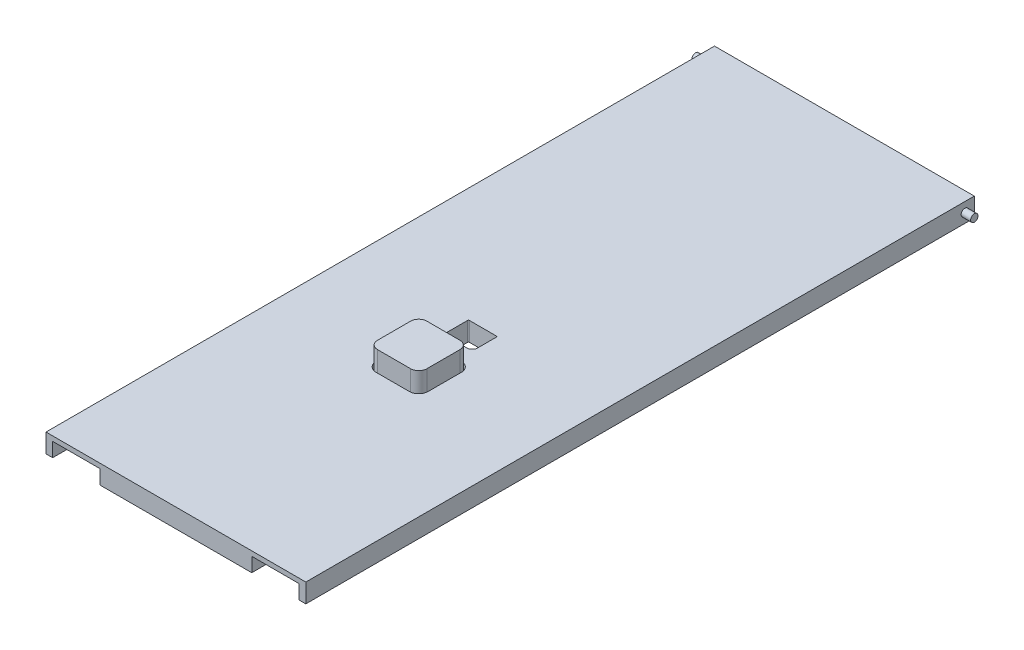
SolidWorks part; units mm, degrees
note: The reader was unsure of these and kept them because the rebuilt part matched: shared geometry of "草图6<3>".
material "PLA"
ref_plane "前视基准面" through (0, 0, 0) normal (0, 0, 1) x (1, 0, 0)
ref_plane "上视基准面" through (0, 0, 0) normal (0, 1, 0) x (1, 0, 0)
ref_plane "右视基准面" through (0, 0, 0) normal (1, 0, 0) x (0, 0, -1)
sketch "草图1" plane through (0, 0, 0) normal (0, 0, 1) x (1, 0, 0)
  line L21 (-13.7, 0) -> (13.7, 0)
  line L24 (13.7, 0) -> (13.7, 2)
  line L25 (13.7, 2) -> (-13.7, 2)
  line L26 (-13.7, 2) -> (-13.7, 0)
  point P0 (0, 0)
  dimension "D1" = 27.4
  dimension "D2" = 2
extrude "凸台-拉伸1" add sketch "草图1" along normal blind 70.5
ref_plane "基准面1" through (0, 0, 0) normal (1, 0, 0) x (0, 0, -1)
sketch "草图13" plane through (0, 0, 0) normal (1, 0, 0) x (0, 0, -1)
  line L0 (-68.5, 0) -> (-67.1502, 0)
  line L1 (-70.5, 0) -> (0, 0) construction
  line L2 (-67.1502, 0) -> (-67.1502, 1.65)
  line L3 (-68.5, 0) -> (-68.5, -1)
  line L4 (-68.5, -1) -> (-68, -1)
  line L5 (-68, -1) -> (-68, 1)
  line L10 (-68.5, 0) -> (-68.9362, 0)
  line L11 (-67.1502, 1.65) -> (-68.65, 1.65)
  line L12 (-68.9362, 0) -> (-68.9362, 0.4164)
  arc A2 (-68, 1) -> (-68.9362, 0.4164) centre (-68.65, 1) ccw
  arc A3 (-68.5, 0) -> (-68.9362, 0.4164) centre (-69.3765, -0.4815) ccw
  arc A4 (-68.65, 1.65) -> (-68.9362, 0.4164) centre (-68.65, 1) ccw
  dimension "D2" = 1.3498
  dimension "D3" = 1.65
  dimension "D1" = 0
extrude "切除-拉伸5" cut sketch "草图13" against normal mid plane 5
fillet "圆角4" radius 0.1 1 edges at (0, 0, 68.9362)
sketch "草图14" plane through (-13.7, 0, 0) normal (-1, 0, 0) x (0, 0, 1)
  line L0 (1.4, 2) -> (1.4, 1) construction
  line L1 (0.6, 1) -> (0.6, 2) construction
  line L2 (1.4, 2) -> (1.4, 1)
  line L3 (0.6, 1) -> (0.6, 2)
  arc A0 (0.6, 1) -> (1.4, 1) centre (1, 1) ccw construction
  arc A1 (0.6, 1) -> (1.4, 1) centre (1, 1) ccw
  circle A2 centre (1, 1) radius 0.39
  dimension "D1" = 0.78
extrude "凸台-拉伸7" add sketch "草图14" along normal blind 1 contours A2
sketch "草图15" plane through (13.7, 0, 0) normal (1, 0, 0) x (0, 0, -1)
  circle A0 centre (-1, 1) radius 0.39 construction
  circle A1 centre (-1, 1) radius 0.39
extrude "凸台-拉伸8" add sketch "草图15" along normal blind 1
sketch "草图16" plane through (0, 0, 70.5) normal (0, 0, 1) x (1, 0, 0)
  line L0 (0, 0) -> (0, 2) construction
  line L1 (13.7, 2) -> (-13.7, 2) construction
  line L2 (-13.7, 0) -> (13.7, 0) construction
  line L3 (-13, 1.5) -> (-8, 1.5)
  line L4 (-13, 1.5) -> (-13, 0)
  line L5 (-13, 0) -> (-8, 0)
  line L6 (-8, 1.5) -> (-8, 0)
  line L7 (13, 0) -> (8, 0)
  line L8 (8, 1.5) -> (8, 0)
  line L9 (13, 1.5) -> (8, 1.5)
  line L10 (13, 1.5) -> (13, 0)
  dimension "D1" = 8
  dimension "D2" = 5
  dimension "D3" = 1.5
extrude "切除-拉伸6" cut sketch "草图16" against normal blind 5
sketch "草图4" plane through (0, 2, 0) normal (0, 1, 0) x (1, 0, 0)
  line L0 (1.8997, -42.991) -> (-1.9003, -46.791) construction
  line L2 (-2.7503, -42.141) -> (2.7497, -42.141)
  line L3 (-2.7503, -42.141) -> (-2.7503, -47.641)
  line L4 (-2.7503, -47.641) -> (2.7497, -47.641)
  line L5 (2.7497, -42.141) -> (2.7497, -47.641)
  line L6 (-2.7503, -42.141) -> (2.7497, -47.641) construction
  line L7 (-2.7503, -47.641) -> (2.7497, -42.141) construction
  line L8 (1.2997, -47.391) -> (2.4997, -46.191)
  line L9 (2.4997, -46.191) -> (2.4997, -43.591)
  line L10 (2.4997, -43.591) -> (1.2997, -42.391)
  line L11 (1.2997, -42.391) -> (-1.3003, -42.391)
  line L12 (-1.3003, -42.391) -> (-2.5003, -43.591)
  line L13 (-2.5003, -43.591) -> (-2.5003, -46.191)
  line L14 (-2.5003, -46.191) -> (-1.3003, -47.391)
  line L15 (-1.3003, -47.391) -> (1.2997, -47.391)
  line L16 (1.2997, -47.391) -> (2.4997, -46.191) construction
  line L17 (2.4997, -46.191) -> (2.4997, -43.591) construction
  line L18 (2.4997, -43.591) -> (1.2997, -42.391) construction
  line L19 (1.2997, -42.391) -> (-1.3003, -42.391) construction
  line L20 (-1.3003, -42.391) -> (-2.5003, -43.591) construction
  line L21 (-2.5003, -43.591) -> (-2.5003, -46.191) construction
  line L22 (-2.5003, -46.191) -> (-1.3003, -47.391) construction
  line L23 (-1.3003, -47.391) -> (1.2997, -47.391) construction
  point P6 (-0.0003, -44.891)
  dimension "D2" = 5.5
  dimension "D1" = 0
extrude "切除-拉伸2" cut sketch "草图4" against normal through all
fillet "圆角1" radius 1 4 edges at (-2.7503, 1, 47.641) (2.7497, 1, 47.641) (2.7497, 1, 42.141) (-2.7503, 1, 42.141)
sketch "草图5" plane through (0, 0, 0) normal (0, -1, 0) x (1, 0, 0)
  line L0 (-2.6003, 46.641) -> (-2.6003, 43.141)
  line L1 (-1.7503, 42.291) -> (1.7497, 42.291)
  line L2 (2.5997, 43.141) -> (2.5997, 46.641)
  line L3 (1.7497, 47.491) -> (-1.7503, 47.491)
  line L4 (-2.7503, 46.641) -> (-2.7503, 43.141)
  line L5 (1.7497, 47.641) -> (-1.7503, 47.641)
  line L6 (2.7497, 43.141) -> (2.7497, 46.641)
  line L7 (-1.7503, 42.141) -> (1.7497, 42.141)
  line L8 (-2.7503, 46.641) -> (-2.7503, 43.141) construction
  line L9 (1.7497, 47.641) -> (-1.7503, 47.641) construction
  line L10 (2.7497, 43.141) -> (2.7497, 46.641) construction
  line L11 (-1.7503, 42.141) -> (1.7497, 42.141) construction
  arc A0 (-2.6003, 43.141) -> (-1.7503, 42.291) centre (-1.7503, 43.141) ccw
  arc A1 (1.7497, 42.291) -> (2.5997, 43.141) centre (1.7497, 43.141) ccw
  arc A2 (2.5997, 46.641) -> (1.7497, 47.491) centre (1.7497, 46.641) ccw
  arc A3 (-1.7503, 47.491) -> (-2.6003, 46.641) centre (-1.7503, 46.641) ccw
  arc A4 (-1.7503, 47.641) -> (-2.7503, 46.641) centre (-1.7503, 46.641) ccw
  arc A5 (2.7497, 46.641) -> (1.7497, 47.641) centre (1.7497, 46.641) ccw
  arc A6 (1.7497, 42.141) -> (2.7497, 43.141) centre (1.7497, 43.141) ccw
  arc A7 (-2.7503, 43.141) -> (-1.7503, 42.141) centre (-1.7503, 43.141) ccw
  arc A8 (-1.7503, 47.641) -> (-2.7503, 46.641) centre (-1.7503, 46.641) ccw construction
  arc A9 (2.7497, 46.641) -> (1.7497, 47.641) centre (1.7497, 46.641) ccw construction
  arc A10 (1.7497, 42.141) -> (2.7497, 43.141) centre (1.7497, 43.141) ccw construction
  arc A11 (-2.7503, 43.141) -> (-1.7503, 42.141) centre (-1.7503, 43.141) ccw construction
  dimension "D1" = 0
  dimension "D2" = 0.15
extrude "凸台-拉伸3" add sketch "草图5" against normal blind 4 separate body
sketch "草图6" plane through (0, 0, 0) normal (0, -1, 0) x (1, 0, 0)
  line L0 (-2.0833, 47.423) -> (-4.788, 46.271)
  line L1 (-4.788, 43.5109) -> (-2.0833, 42.3589)
  line L2 (-4.2003, 44.891) -> (-2.6003, 44.891) construction
  line L3 (-0.0003, 42.291) -> (-0.0003, 47.491) construction
  line L5 (-2.6003, 46.641) -> (-2.6003, 43.141)
  line L6 (-1.7503, 42.291) -> (1.7497, 42.291)
  line L7 (2.5997, 43.141) -> (2.5997, 46.641)
  line L12 (1.7497, 47.491) -> (-1.7503, 47.491)
  line L13 (-2.6003, 46.641) -> (-2.6003, 43.141)
  line L14 (-1.7503, 42.291) -> (1.7497, 42.291)
  line L15 (2.5997, 43.141) -> (2.5997, 46.641)
  line L16 (1.7497, 47.491) -> (-1.7503, 47.491)
  line L17 (2.0828, 47.423) -> (4.7875, 46.271)
  line L18 (4.7875, 43.5109) -> (2.0828, 42.3589)
  arc A2 (-4.788, 46.271) -> (-4.788, 43.5109) centre (-4.2003, 44.891) ccw
  circle A12 centre (-4.2003, 44.891) radius 0.9
  circle A13 centre (4.1997, 44.891) radius 0.9
  arc A14 (4.7875, 46.271) -> (4.7875, 43.5109) centre (4.1997, 44.891) cw
  arc A15 (-1.7503, 47.491) -> (-2.6003, 46.641) centre (-1.7503, 46.641) ccw
  arc A16 (-2.6003, 43.141) -> (-1.7503, 42.291) centre (-1.7503, 43.141) ccw
  arc A17 (1.7497, 42.291) -> (2.5997, 43.141) centre (1.7497, 43.141) ccw
  arc A18 (2.5997, 46.641) -> (1.7497, 47.491) centre (1.7497, 46.641) ccw
  arc A19 (-1.7503, 47.491) -> (-2.6003, 46.641) centre (-1.7503, 46.641) ccw
  arc A20 (-2.6003, 43.141) -> (-1.7503, 42.291) centre (-1.7503, 43.141) ccw
  arc A21 (1.7497, 42.291) -> (2.5997, 43.141) centre (1.7497, 43.141) ccw
  arc A22 (2.5997, 46.641) -> (1.7497, 47.491) centre (1.7497, 46.641) ccw
  arc M15 (-1.7503, 47.491) -> (-2.6003, 46.641) centre (-1.7503, 46.641) ccw
  line M16 (-2.6003, 46.641) -> (-2.6003, 43.141)
  arc M17 (-2.6003, 43.141) -> (-1.7503, 42.291) centre (-1.7503, 43.141) ccw
  line M18 (-1.7503, 42.291) -> (1.7497, 42.291)
  arc M19 (1.7497, 42.291) -> (2.5997, 43.141) centre (1.7497, 43.141) ccw
  line M20 (2.5997, 43.141) -> (2.5997, 46.641)
  arc M21 (2.5997, 46.641) -> (1.7497, 47.491) centre (1.7497, 46.641) ccw
  line M22 (1.7497, 47.491) -> (-1.7503, 47.491)
  dimension "D2" = 3
  dimension "D3" = 1.8
  dimension "D4" = 1.6
  dimension "D1" = 0
extrude "凸台-拉伸4" add sketch "草图6" along normal blind 2 contours L0 A2 L1 A12 M17 M16 M15 | M22 M15 M16 M17 M18 M19 M20 M21 | A14 L17 L18 A13 M21 M20 M19
sketch "草图7" plane through (0, 0, 0) normal (0, -1, 0) x (1, 0, 0)
  circle A0 centre (4.1997, 44.891) radius 0.75
  circle A1 centre (-4.2003, 44.891) radius 0.75
  dimension "D1" = 1.5
extrude "凸台-拉伸5" add sketch "草图7" along normal offset from surface (4.5 mm away) 2.5 up to face at (-0.0003, -2, 44.891) offset beyond the face yes
extrude "凸台-拉伸6" add sketch "草图6<3>" along normal blind 3 from surface at 2 starting at face at (-0.0003, -2, 44.891)
sketch "草图6<3>" plane through (0, 0, 0) normal (0, -1, 0) x (1, 0, 0) same geometry as "草图6"
sketch "草图17" plane through (0, 2, 0) normal (0, 1, 0) x (1, 0, 0)
  line L0 (1.3813, -40.2814) -> (1.3813, -38.081) construction
  line L1 (1.3813, -40.2814) -> (1.0388, -40.6239) construction
  line L2 (-1.5616, -40.6239) -> (1.0388, -40.6239) construction
  line L3 (-1.6612, -38.081) -> (-1.6612, -40.5243) construction
  line L4 (13.7, 0) -> (-13.7, 0)
  line L5 (-13.7, 0) -> (-13.7, -70.5)
  line L6 (-13.7, -70.5) -> (13.7, -70.5)
  line L7 (13.7, -70.5) -> (13.7, 0)
  line L8 (13.7, 0) -> (-13.7, 0)
  line L9 (-13.7, 0) -> (-13.7, -70.5)
  line L10 (-13.7, -70.5) -> (13.7, -70.5)
  line L11 (13.7, -70.5) -> (13.7, 0)
  line L12 (1.2817, -37.9814) -> (-1.5616, -37.9814) construction
  line L13 (1.3813, -40.2814) -> (1.3813, -38.081)
  line L14 (1.3813, -40.2814) -> (1.0388, -40.6239)
  line L15 (-1.5616, -40.6239) -> (1.0388, -40.6239)
  line L16 (-1.6612, -38.081) -> (-1.6612, -40.5243)
  line L17 (1.2817, -37.9814) -> (-1.5616, -37.9814)
  ellipse E0 centre (-1.5608, -40.5235) end of major axis (-1.6321, -40.5948) minor radius 0.1 (-1.6612, -40.5243) -> (-1.5616, -40.6239) ccw construction
  ellipse E1 centre (-1.5608, -38.0818) end of major axis (-1.6321, -38.0105) minor radius 0.1 (-1.5616, -37.9814) -> (-1.6612, -38.081) ccw construction
  ellipse E2 centre (1.2809, -38.0818) end of major axis (1.3522, -38.0105) minor radius 0.1 (1.3813, -38.081) -> (1.2817, -37.9814) ccw construction
  ellipse E3 centre (-1.5608, -40.5235) end of major axis (-1.6321, -40.5948) minor radius 0.1 (-1.6612, -40.5243) -> (-1.5616, -40.6239) ccw
  ellipse E4 centre (-1.5608, -38.0818) end of major axis (-1.6321, -38.0105) minor radius 0.1 (-1.5616, -37.9814) -> (-1.6612, -38.081) ccw
  ellipse E5 centre (1.2809, -38.0818) end of major axis (1.3522, -38.0105) minor radius 0.1 (1.3813, -38.081) -> (1.2817, -37.9814) ccw
  dimension "D1" = 0
extrude "切除-拉伸7" cut sketch "草图17" against normal up to next (2 mm away) contours E3 L15 L14 L13 E5 L17 E4 L16
